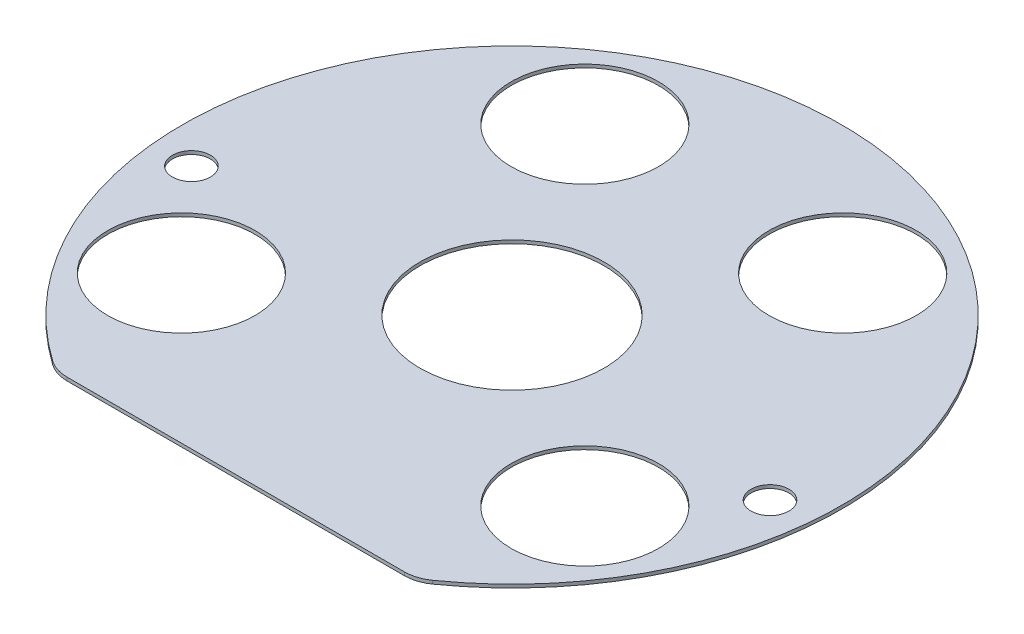
SolidWorks part; units mm, degrees
material "6063-T6"
ref_plane "Front Plane" through (0, 0, 0) normal (0, 0, 1) x (1, 0, 0)
ref_plane "Top Plane" through (0, 0, 0) normal (0, 1, 0) x (1, 0, 0)
ref_plane "Right Plane" through (0, 0, 0) normal (1, 0, 0) x (0, 0, -1)
sketch "Sketch1" plane through (0, 0, 0) normal (0, 1, 0) x (1, 0, 0)
  line L0 (0, 89.5) -> (0, -75) construction
  line L2 (-89.5, 0) -> (89.5, 0) construction
  line L3 (-48.839, -75) -> (48.839, -75)
  arc A0 (48.839, -75) -> (-48.839, -75) centre (0, 0) ccw
  dimension "D1" = 179
  dimension "D2" = 75
extrude "Boss-Extrude1" add sketch "Sketch1" against normal blind 0.91
sketch "Sketch9" plane through (0, 0, 0) normal (0, 1, 0) x (1, 0, 0)
  line L0 (0, 89.5) -> (0, -75) construction
  line L1 (48.839, -75) -> (-48.839, -75) construction
  line L2 (78.5412, -8.5017) -> (-78.5412, -8.5017) construction
  arc A12 (48.839, -75) -> (-48.839, -75) centre (0, 0) ccw construction
  circle A13 centre (78.5412, -8.5017) radius 5.15
  circle A15 centre (-78.5412, -8.5017) radius 5.15
  point P8 (0, -8.5017)
  dimension "D3" = 10.3
  dimension "D4" = 10.3
  dimension "D2" = 66.4983
  dimension "D1" = 157.0824
extrude "Cut-Extrude3" cut sketch "Sketch9" against normal through all contours A15 | A13
sketch "Vision Pattern" plane through (0, 0, 0) normal (0, 1, 0) x (1, 0, 0)
  line L0 (64.8074, -55) -> (-64.8074, -55) construction
  line L1 (0, 0) -> (0, -55) construction
  circle A0 centre (0, 0) radius 85 construction
  circle A1 centre (0, 0) radius 25
  circle A2 centre (54.7723, -35) radius 20
  circle A3 centre (-54.7723, -35) radius 20
  circle A4 centre (35, 54.7723) radius 20
  circle A5 centre (-35, 54.7723) radius 20
  circle A6 centre (0, 0) radius 65 construction
  dimension "D1" = 170
  dimension "D3" = 50
  dimension "D4" = 40
  dimension "D2" = 55
  dimension "D5" = 35
  dimension "D8" = 65
  dimension "D6" = 35
  dimension "D7" = 35
extrude "Cut-Extrude4" cut sketch "Vision Pattern" against normal through all
fillet "Fillet1" radius 10 2 edges at (48.839, -0.455, 75) (-48.839, -0.455, 75)
equation "\"D4@Sketch9\"=\"D3@Sketch9\""
equation "\"D1@Vision Pattern\" = 85 * 2"
equation "\"D7@Vision Pattern\"=\"D6@Vision Pattern\""
equation "\"20Gauge\"= .911"
